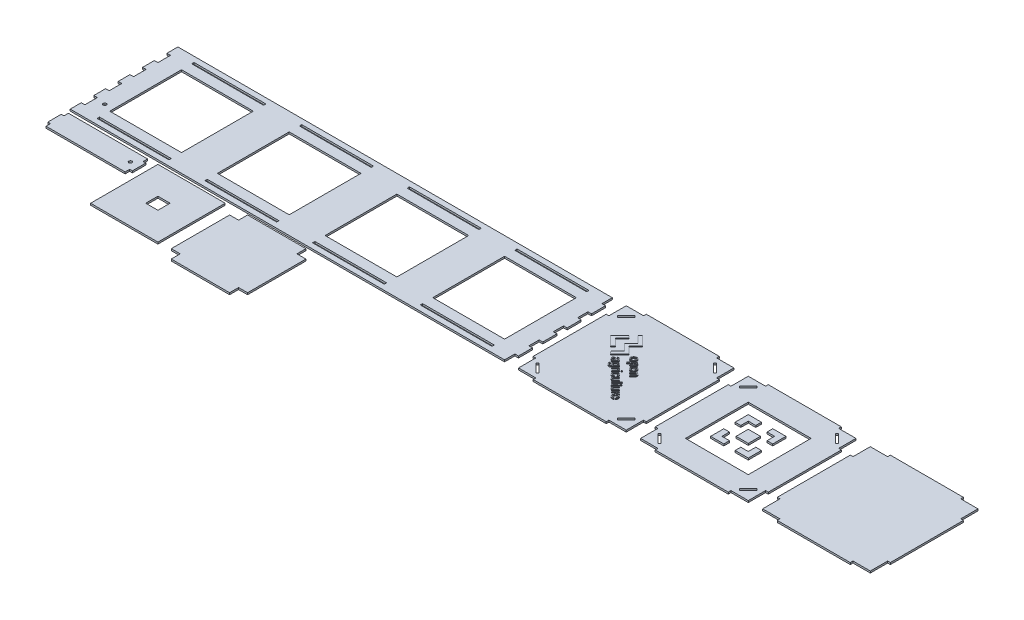
SolidWorks part; units mm, degrees
ref_plane "Front" through (0, 0, 0) normal (0, 0, 1) x (1, 0, 0)
ref_plane "Top" through (0, 0, 0) normal (0, 1, 0) x (1, 0, 0)
ref_plane "Right" through (0, 0, 0) normal (1, 0, 0) x (0, 0, -1)
sketch "Sketch1" plane through (0, 0, 0) normal (0, 1, 0) x (1, 0, 0)
  line L0 (0, 0) -> (228.6, 0) construction
  line L2 (-76.2, 76.2) -> (-76.2, -76.2) construction
  line L4 (76.2, 76.2) -> (76.2, -76.2) construction
  line L5 (-76.2, 76.2) -> (76.2, -76.2) construction
  line L6 (-76.2, -76.2) -> (76.2, 76.2) construction
  line L11 (76.2, 76.2) -> (228.6, 76.2)
  line L12 (76.2, 76.2) -> (76.2, -76.2) construction
  line L13 (76.2, -76.2) -> (228.6, -76.2)
  line L14 (228.6, 76.2) -> (228.6, -76.2) construction
  line L19 (-76.2, -76.2) -> (-228.6, -76.2)
  line L20 (-76.2, -76.2) -> (-76.2, 76.2) construction
  line L21 (-76.2, 76.2) -> (-228.6, 76.2)
  line L28 (76.2, -76.2) -> (-76.2, -76.2)
  line L34 (76.2, 76.2) -> (-76.2, 76.2)
  line L35 (-228.6, 76.2) -> (-228.6, -76.2) construction
  line L43 (-228.6, 76.2) -> (-381, 76.2)
  line L44 (-381, 76.2) -> (-381, -76.2) construction
  line L45 (-381, -76.2) -> (-228.6, -76.2)
  line L46 (228.6, 76.2) -> (228.6, 61.6712)
  line L47 (228.6, 61.6712) -> (233.68, 61.6712)
  line L48 (233.68, 61.6712) -> (233.68, 41.7322)
  line L49 (233.68, 41.7322) -> (228.6, 41.7322)
  line L50 (228.6, 41.7322) -> (228.6, 27.2034)
  line L51 (228.6, 27.2034) -> (233.68, 27.2034)
  line L63 (233.68, 27.2034) -> (233.68, 7.2644)
  line L64 (233.68, 7.2644) -> (228.6, 7.2644)
  line L65 (228.6, 7.2644) -> (228.6, -7.2644)
  line L66 (228.6, -7.2644) -> (233.68, -7.2644)
  line L67 (233.68, -7.2644) -> (233.68, -27.2034)
  line L68 (233.68, -27.2034) -> (228.6, -27.2034)
  line L69 (228.6, -27.2034) -> (228.6, -41.7322)
  line L70 (228.6, -41.7322) -> (233.68, -41.7322)
  line L71 (233.68, -41.7322) -> (233.68, -61.6712)
  line L72 (233.68, -61.6712) -> (228.6, -61.6712)
  line L73 (228.6, -61.6712) -> (228.6, -76.2)
  line L74 (-381, 76.2) -> (-386.08, 76.2)
  line L76 (-386.08, 60.5917) -> (-381, 60.5917)
  line L78 (-381, 42.8117) -> (-386.08, 42.8117)
  line L80 (-386.08, 26.1239) -> (-381, 26.1239)
  line L82 (-381, 8.3439) -> (-386.08, 8.3439)
  line L84 (-386.08, -8.3439) -> (-381, -8.3439)
  line L86 (-381, -26.1239) -> (-386.08, -26.1239)
  line L88 (-386.08, -42.8117) -> (-381, -42.8117)
  line L90 (-381, -60.5917) -> (-386.08, -60.5917)
  line L92 (-386.08, -76.2) -> (-381, -76.2)
  line L93 (233.68, 17.2339) -> (-381, 17.2339) construction
  line L94 (-381, 51.7017) -> (233.68, 51.7017) construction
  line L95 (-386.08, 76.2) -> (-386.08, 60.5917)
  line L96 (-386.08, 42.8117) -> (-386.08, 26.1239)
  line L97 (-381, 60.5917) -> (-381, 42.8117)
  line L98 (-381, 26.1239) -> (-381, 8.3439)
  line L99 (-381, -8.3439) -> (-381, -26.1239)
  line L100 (-381, -42.8117) -> (-381, -60.5917)
  line L101 (-381, -51.7017) -> (233.68, -51.7017) construction
  line L102 (-381, -17.2339) -> (233.68, -17.2339) construction
  line L103 (-386.08, 8.3439) -> (-386.08, -8.3439)
  line L104 (-386.08, -26.1239) -> (-386.08, -42.8117)
  line L105 (-386.08, -60.5917) -> (-386.08, -76.2)
  point P0 (0, 0)
  point P56 (-406.2048, -26.1239)
  point P57 (-388.4215, 60.5917)
  point P58 (-409.3463, 42.8117)
  point P59 (-388.4448, 60.5917)
  dimension "D1" = 152.4
  dimension "D2" = 152.4
  dimension "D3" = 5.08
  dimension "D4" = 19.939
  dimension "D5" = 17.78
extrude "Boss-Extrude1" add sketch "Sketch1" along normal blind 2.54
sketch "Sketch4" plane through (0, 2.54, 0) normal (0, 1, 0) x (1, 0, 0)
  line L0 (-228.6, 76.2) -> (-228.6, -76.2) construction
  line L1 (-228.6, 76.2) -> (-228.6, -76.2)
  line L2 (-76.2, 76.2) -> (-76.2, -76.2) construction
  line L3 (-76.2, 76.2) -> (-76.2, -76.2)
  line L4 (76.2, 76.2) -> (76.2, -76.2) construction
  line L5 (76.2, 76.2) -> (76.2, -76.2)
sketch "Sketch5" plane through (0, 2.54, 0) normal (0, 1, 0) x (1, 0, 0)
  line L0 (-381, -8.3439) -> (-381, 8.3439) construction
  line L1 (-228.6, 0) -> (-381, 0) construction
  line L2 (-228.6, 76.2) -> (-228.6, -76.2) construction
  line L3 (-228.6, 0) -> (-76.2, 0) construction
  line L4 (-76.2, 76.2) -> (-76.2, -76.2) construction
  line L5 (-76.2, 0) -> (76.2, 0) construction
  line L6 (76.2, 76.2) -> (76.2, -76.2) construction
  line L7 (76.2, 0) -> (228.6, 0) construction
  line L8 (228.6, -7.2644) -> (228.6, 7.2644) construction
  line L9 (-304.8, 0) -> (-304.8, -76.2) construction
  line L10 (-386.08, -76.2) -> (228.6, -76.2) construction
  line L11 (-152.4, 0) -> (-152.4, -76.2) construction
  line L12 (0, 0) -> (0, -76.2) construction
  line L13 (152.4, 0) -> (152.4, -76.2) construction
  line L14 (-254, -68.58) -> (-254, -76.2) construction
  line L15 (-355.6, -65.278) -> (-254, -65.278)
  line L16 (-355.6, -65.278) -> (-355.6, -68.58)
  line L17 (-355.6, -68.58) -> (-254, -68.58)
  line L18 (-254, -65.278) -> (-254, -68.58)
  line L19 (-355.6, -65.278) -> (-254, -68.58) construction
  line L20 (-355.6, -68.58) -> (-254, -65.278) construction
  line L21 (-203.2, -65.278) -> (-101.6, -65.278)
  line L22 (-203.2, -65.278) -> (-203.2, -68.58)
  line L23 (-203.2, -68.58) -> (-101.6, -68.58)
  line L24 (-101.6, -65.278) -> (-101.6, -68.58)
  line L25 (-203.2, -65.278) -> (-101.6, -68.58) construction
  line L26 (-203.2, -68.58) -> (-101.6, -65.278) construction
  line L27 (-50.8, -68.58) -> (50.8, -68.58)
  line L28 (-50.8, -68.58) -> (-50.8, -65.278)
  line L29 (-50.8, -65.278) -> (50.8, -65.278)
  line L30 (50.8, -68.58) -> (50.8, -65.278)
  line L31 (-50.8, -68.58) -> (50.8, -65.278) construction
  line L32 (-50.8, -65.278) -> (50.8, -68.58) construction
  line L33 (101.6, -68.58) -> (203.2, -68.58)
  line L34 (101.6, -68.58) -> (101.6, -65.278)
  line L35 (101.6, -65.278) -> (203.2, -65.278)
  line L36 (203.2, -68.58) -> (203.2, -65.278)
  line L37 (101.6, -68.58) -> (203.2, -65.278) construction
  line L38 (101.6, -65.278) -> (203.2, -68.58) construction
  line L39 (101.6, 65.278) -> (203.2, 68.58) construction
  line L40 (101.6, 68.58) -> (203.2, 65.278) construction
  line L41 (-50.8, 65.278) -> (50.8, 68.58) construction
  line L42 (-50.8, 68.58) -> (50.8, 65.278) construction
  line L43 (-203.2, 68.58) -> (-101.6, 65.278) construction
  line L44 (-203.2, 65.278) -> (-101.6, 68.58) construction
  line L45 (-355.6, 68.58) -> (-254, 65.278) construction
  line L46 (-355.6, 65.278) -> (-254, 68.58) construction
  line L47 (-254, 68.58) -> (-254, 76.2) construction
  line L48 (203.2, 68.58) -> (203.2, 65.278)
  line L49 (101.6, 65.278) -> (203.2, 65.278)
  line L50 (101.6, 68.58) -> (101.6, 65.278)
  line L51 (101.6, 68.58) -> (203.2, 68.58)
  line L52 (50.8, 68.58) -> (50.8, 65.278)
  line L53 (-50.8, 65.278) -> (50.8, 65.278)
  line L54 (-50.8, 68.58) -> (-50.8, 65.278)
  line L55 (-50.8, 68.58) -> (50.8, 68.58)
  line L56 (-101.6, 65.278) -> (-101.6, 68.58)
  line L57 (-203.2, 68.58) -> (-101.6, 68.58)
  line L58 (-203.2, 65.278) -> (-203.2, 68.58)
  line L59 (-203.2, 65.278) -> (-101.6, 65.278)
  line L60 (-254, 65.278) -> (-254, 68.58)
  line L61 (-355.6, 68.58) -> (-254, 68.58)
  line L62 (-355.6, 65.278) -> (-355.6, 68.58)
  line L63 (-355.6, 65.278) -> (-254, 65.278)
  line L65 (-355.6, 50.8) -> (-254, 50.8)
  line L66 (-355.6, 50.8) -> (-355.6, -50.8)
  line L67 (-355.6, -50.8) -> (-254, -50.8)
  line L68 (-254, 50.8) -> (-254, -50.8)
  line L69 (-355.6, 50.8) -> (-254, -50.8) construction
  line L70 (-355.6, -50.8) -> (-254, 50.8) construction
  line L71 (-203.2, 50.8) -> (-101.6, 50.8)
  line L72 (-203.2, 50.8) -> (-203.2, -50.8)
  line L73 (-203.2, -50.8) -> (-101.6, -50.8)
  line L74 (-101.6, 50.8) -> (-101.6, -50.8)
  line L75 (-203.2, 50.8) -> (-101.6, -50.8) construction
  line L76 (-203.2, -50.8) -> (-101.6, 50.8) construction
  line L77 (-50.8, 50.8) -> (50.8, 50.8)
  line L78 (-50.8, 50.8) -> (-50.8, -50.8)
  line L79 (-50.8, -50.8) -> (50.8, -50.8)
  line L80 (50.8, 50.8) -> (50.8, -50.8)
  line L81 (-50.8, 50.8) -> (50.8, -50.8) construction
  line L82 (-50.8, -50.8) -> (50.8, 50.8) construction
  line L83 (101.6, 50.8) -> (203.2, 50.8)
  line L84 (101.6, 50.8) -> (101.6, -50.8)
  line L85 (101.6, -50.8) -> (203.2, -50.8)
  line L86 (203.2, 50.8) -> (203.2, -50.8)
  line L87 (101.6, 50.8) -> (203.2, -50.8) construction
  line L88 (101.6, -50.8) -> (203.2, 50.8) construction
  circle A0 centre (-367.6, -45.8) radius 2.2225
  point P27 (-304.8, -66.929)
  point P32 (-152.4, -66.929)
  point P37 (0, -66.929)
  point P42 (152.4, -66.929)
  point P66 (152.4, 66.929)
  point P67 (0, 66.929)
  point P68 (-152.4, 66.929)
  point P69 (-304.8, 66.929)
  dimension "D5" = 4.445
  dimension "D7" = 5
  dimension "D1" = 7.62
  dimension "D2" = 3.302
  dimension "D3" = 101.6
  dimension "D4" = 101.6
  dimension "D6" = 12
extrude "Cut-Extrude2" cut sketch "Sketch5" against normal through all
sketch "Sketch6" plane through (0, 0, 0) normal (0, 1, 0) x (1, 0, 0)
  line L0 (0, 0) -> (324.5769, 0) construction
  line L1 (324.5769, 0) -> (324.5769, 78.105) construction
  line L2 (248.3769, 76.2) -> (400.7769, 76.2) construction
  line L3 (248.3769, 76.2) -> (248.3769, -76.2) construction
  line L4 (248.3769, -76.2) -> (400.7769, -76.2) construction
  line L5 (400.7769, 76.2) -> (400.7769, -76.2) construction
  line L6 (248.3769, 76.2) -> (400.7769, -76.2) construction
  line L7 (248.3769, -76.2) -> (400.7769, 76.2) construction
  line L8 (324.5769, 0) -> (402.6819, 0) construction
  line L9 (324.5769, 0) -> (324.5769, -78.105) construction
  line L10 (248.3769, 51.689) -> (248.3769, 76.2)
  line L11 (272.8879, 80.01) -> (376.2659, 80.01)
  line L12 (272.8879, 80.01) -> (272.8879, 76.2)
  line L13 (272.8879, 76.2) -> (376.2659, 76.2) construction
  line L14 (376.2659, 80.01) -> (376.2659, 76.2)
  line L15 (272.8879, 80.01) -> (376.2659, 76.2) construction
  line L16 (272.8879, 76.2) -> (376.2659, 80.01) construction
  line L17 (404.5869, -51.689) -> (400.7769, -51.689)
  line L18 (404.5869, -51.689) -> (404.5869, 51.689)
  line L19 (404.5869, 51.689) -> (400.7769, 51.689)
  line L20 (400.7769, -51.689) -> (400.7769, 51.689) construction
  line L21 (404.5869, -51.689) -> (400.7769, 51.689) construction
  line L22 (404.5869, 51.689) -> (400.7769, -51.689) construction
  line L23 (272.8879, -80.01) -> (376.2659, -80.01)
  line L24 (272.8879, -80.01) -> (272.8879, -76.2)
  line L25 (272.8879, -76.2) -> (376.2659, -76.2) construction
  line L26 (376.2659, -80.01) -> (376.2659, -76.2)
  line L27 (272.8879, -80.01) -> (376.2659, -76.2) construction
  line L28 (272.8879, -76.2) -> (376.2659, -80.01) construction
  line L29 (244.5669, 51.689) -> (248.3769, 51.689)
  line L30 (244.5669, 51.689) -> (244.5669, -51.689)
  line L31 (244.5669, -51.689) -> (248.3769, -51.689)
  line L32 (248.3769, 51.689) -> (248.3769, -51.689) construction
  line L33 (244.5669, 51.689) -> (248.3769, -51.689) construction
  line L34 (244.5669, -51.689) -> (248.3769, 51.689) construction
  line L35 (248.3769, 76.2) -> (272.8879, 76.2)
  line L36 (376.2659, 76.2) -> (400.7769, 76.2)
  line L37 (400.7769, 76.2) -> (400.7769, 51.689)
  line L38 (400.7769, -51.689) -> (400.7769, -76.2)
  line L39 (400.7769, -76.2) -> (376.2659, -76.2)
  line L40 (272.8879, -76.2) -> (248.3769, -76.2)
  line L41 (248.3769, -76.2) -> (248.3769, -51.689)
  line L42 (417.2869, 51.689) -> (417.2869, -51.689)
  line L43 (417.2869, 51.689) -> (421.0969, 51.689)
  line L44 (421.0969, 51.689) -> (421.0969, 76.2)
  line L45 (421.0969, 76.2) -> (445.6079, 76.2)
  line L46 (445.6079, 80.01) -> (445.6079, 76.2)
  line L47 (445.6079, 80.01) -> (548.9859, 80.01)
  line L48 (548.9859, 80.01) -> (548.9859, 76.2)
  line L49 (548.9859, 76.2) -> (573.4969, 76.2)
  line L50 (573.4969, 76.2) -> (573.4969, 51.689)
  line L51 (577.3069, 51.689) -> (573.4969, 51.689)
  line L52 (577.3069, -51.689) -> (577.3069, 51.689)
  line L53 (577.3069, -51.689) -> (573.4969, -51.689)
  line L54 (573.4969, -51.689) -> (573.4969, -76.2)
  line L55 (573.4969, -76.2) -> (548.9859, -76.2)
  line L56 (548.9859, -80.01) -> (548.9859, -76.2)
  line L57 (445.6079, -80.01) -> (548.9859, -80.01)
  line L58 (445.6079, -80.01) -> (445.6079, -76.2)
  line L59 (445.6079, -76.2) -> (421.0969, -76.2)
  line L60 (421.0969, -76.2) -> (421.0969, -51.689)
  line L61 (417.2869, -51.689) -> (421.0969, -51.689)
  line L62 (421.0969, 76.2) -> (573.4969, -76.2) construction
  line L63 (590.0069, 51.689) -> (590.0069, -51.689)
  line L64 (590.0069, 51.689) -> (593.8169, 51.689)
  line L65 (593.8169, 51.689) -> (593.8169, 76.2)
  line L66 (593.8169, 76.2) -> (618.3279, 76.2)
  line L67 (618.3279, 80.01) -> (618.3279, 76.2)
  line L68 (618.3279, 80.01) -> (721.7059, 80.01)
  line L69 (721.7059, 80.01) -> (721.7059, 76.2)
  line L70 (721.7059, 76.2) -> (746.2169, 76.2)
  line L71 (746.2169, 76.2) -> (746.2169, 51.689)
  line L72 (750.0269, 51.689) -> (746.2169, 51.689)
  line L73 (750.0269, -51.689) -> (750.0269, 51.689)
  line L74 (750.0269, -51.689) -> (746.2169, -51.689)
  line L75 (746.2169, -51.689) -> (746.2169, -76.2)
  line L76 (746.2169, -76.2) -> (721.7059, -76.2)
  line L77 (721.7059, -80.01) -> (721.7059, -76.2)
  line L78 (618.3279, -80.01) -> (721.7059, -80.01)
  line L79 (618.3279, -80.01) -> (618.3279, -76.2)
  line L80 (618.3279, -76.2) -> (593.8169, -76.2)
  line L81 (593.8169, -76.2) -> (593.8169, -51.689)
  line L82 (590.0069, -51.689) -> (593.8169, -51.689)
  line L84 (452.8469, 44.45) -> (541.7469, 44.45)
  line L85 (452.8469, 44.45) -> (452.8469, -44.45)
  line L86 (452.8469, -44.45) -> (541.7469, -44.45)
  line L87 (541.7469, 44.45) -> (541.7469, -44.45)
  line L88 (452.8469, 44.45) -> (541.7469, -44.45) construction
  line L89 (452.8469, -44.45) -> (541.7469, 44.45) construction
  point P22 (246.4719, 0)
  point P67 (497.2969, 0)
  dimension "D1" = 152.4
  dimension "D2" = 152.4
  dimension "D3" = 3.81
  dimension "D4" = 103.378
  dimension "D5" = 324.5769
  dimension "D7" = 12.7
  dimension "D8" = 88.9
  dimension "D6" = 3
extrude "Boss-Extrude2" add sketch "Sketch6" along normal blind 2.54 separate body
sketch "Sketch7" plane through (0, 0, 0) normal (0, 1, 0) x (1, 0, 0)
  line L0 (-355.6, 65.278) -> (-355.6, -46.736) construction
  line L1 (-382.27, -82.55) -> (-270.256, -82.55)
  line L2 (-382.27, -82.55) -> (-382.27, -88.9)
  line L3 (-382.27, -114.3) -> (-270.256, -114.3)
  line L4 (-270.256, -82.55) -> (-270.256, -88.9)
  line L5 (-382.27, -82.55) -> (-270.256, -114.3) construction
  line L6 (-382.27, -114.3) -> (-270.256, -82.55) construction
  line L7 (-355.6, 50.8) -> (-355.6, -50.8) construction
  line L8 (-355.6, -46.736) -> (-355.6, -50.8) construction
  line L9 (248.3769, -51.689) -> (248.3769, -76.2) construction
  line L10 (248.3769, -76.2) -> (272.8879, -76.2) construction
  line L12 (-382.27, -88.9) -> (-386.08, -88.9)
  line L13 (256.6811, -55.3235) -> (269.2534, -67.8958) construction
  line L14 (256.6811, -55.3235) -> (254.3462, -57.6583) construction
  line L15 (254.3462, -57.6583) -> (266.9186, -70.2307) construction
  line L16 (269.2534, -67.8958) -> (266.9186, -70.2307) construction
  line L17 (256.6811, -55.3235) -> (266.9186, -70.2307) construction
  line L18 (254.3462, -57.6583) -> (269.2534, -67.8958) construction
  line L19 (-386.08, -88.9) -> (-386.08, -107.95)
  line L20 (-386.08, -107.95) -> (-382.27, -107.95)
  line L21 (248.3769, -51.689) -> (272.8879, -76.2) construction
  line L22 (261.7998, -62.7771) -> (260.6324, -63.9445) construction
  line L23 (-382.27, -107.95) -> (-382.27, -114.3)
  line L24 (-270.256, -88.9) -> (-266.446, -88.9)
  line L25 (-266.446, -88.9) -> (-266.446, -107.95)
  line L26 (-266.446, -107.95) -> (-270.256, -107.95)
  line L27 (-270.256, -107.95) -> (-270.256, -114.3)
  line L28 (-386.08, -76.2) -> (228.6, -76.2) construction
  line L29 (-386.08, -60.5917) -> (-386.08, -76.2) construction
  point P0 (-326.263, -98.425)
  point P14 (261.7998, -62.7771)
  point P31 (-259.0782, -103.78)
  dimension "D1" = 31.75
  dimension "D2" = 4.064
  dimension "D3" = 3.302
  dimension "D4" = 19.05
  dimension "D5" = 17.78
  dimension "D6" = 3.81
  dimension "D7" = 6.35
extrude "Boss-Extrude3" add sketch "Sketch7" along normal blind 2.54 separate body
sketch "Sketch8" plane through (0, 2.54, 0) normal (0, 1, 0) x (1, 0, 0)
  line L0 (254.3462, -57.6583) -> (266.9186, -70.2307) construction
  line L1 (269.2534, -67.8958) -> (266.9186, -70.2307) construction
  line L2 (256.6811, -55.3235) -> (269.2534, -67.8958) construction
  line L3 (256.6811, -55.3235) -> (254.3462, -57.6583) construction
  line L4 (254.3462, -57.6583) -> (266.9186, -70.2307)
  line L5 (269.2534, -67.8958) -> (266.9186, -70.2307)
  line L6 (256.6811, -55.3235) -> (269.2534, -67.8958)
  line L7 (256.6811, -55.3235) -> (254.3462, -57.6583)
  line L8 (248.3769, 76.2) -> (400.7769, -76.2) construction
  line L9 (269.2534, 67.8958) -> (256.6811, 55.3235)
  line L10 (269.2534, 67.8958) -> (266.9186, 70.2307)
  line L11 (266.9186, 70.2307) -> (254.3462, 57.6583)
  line L12 (256.6811, 55.3235) -> (254.3462, 57.6583)
  line L13 (392.4727, 55.3235) -> (379.9003, 67.8958)
  line L14 (392.4727, 55.3235) -> (394.8076, 57.6583)
  line L15 (394.8076, 57.6583) -> (382.2352, 70.2307)
  line L16 (379.9003, 67.8958) -> (382.2352, 70.2307)
  line L17 (379.9003, -67.8958) -> (392.4727, -55.3235)
  line L18 (379.9003, -67.8958) -> (382.2352, -70.2307)
  line L19 (382.2352, -70.2307) -> (394.8076, -57.6583)
  line L20 (392.4727, -55.3235) -> (394.8076, -57.6583)
  line L21 (421.0969, -51.689) -> (445.6079, -76.2) construction
  line L22 (427.0662, -57.6583) -> (429.4011, -55.3235)
  line L23 (429.4011, -55.3235) -> (441.9734, -67.8958)
  line L24 (441.9734, -67.8958) -> (439.6386, -70.2307)
  line L25 (433.3524, -63.9445) -> (435.6873, -61.6096) construction
  line L26 (427.0662, -57.6583) -> (439.6386, -70.2307)
  line L27 (421.0969, 76.2) -> (573.4969, -76.2) construction
  line L28 (429.4011, 55.3235) -> (427.0662, 57.6583)
  line L29 (439.6386, 70.2307) -> (427.0662, 57.6583)
  line L30 (439.6386, 70.2307) -> (441.9734, 67.8958)
  line L31 (441.9734, 67.8958) -> (429.4011, 55.3235)
  line L32 (552.6203, 67.8958) -> (554.9552, 70.2307)
  line L33 (567.5276, 57.6583) -> (554.9552, 70.2307)
  line L34 (567.5276, 57.6583) -> (565.1927, 55.3235)
  line L35 (565.1927, 55.3235) -> (552.6203, 67.8958)
  line L36 (565.1927, -55.3235) -> (567.5276, -57.6583)
  line L37 (554.9552, -70.2307) -> (567.5276, -57.6583)
  line L38 (554.9552, -70.2307) -> (552.6203, -67.8958)
  line L39 (552.6203, -67.8958) -> (565.1927, -55.3235)
  circle A0 centre (324.5769, 0) radius 20.7898 construction
  circle A1 centre (324.5769, 0) radius 20.7898 construction
  circle A2 centre (324.5769, 0) radius 20.7898 construction
  circle A3 centre (324.5769, 0) radius 20.7898 construction
  circle A4 centre (497.2969, 0) radius 62.8618 construction
  point P28 (324.5769, 0)
  point P43 (533.3272, -100.1408)
  point P44 (0, 0)
  point P58 (497.2969, 0)
  dimension "D1" = 4
  dimension "D2" = 4
extrude "Cut-Extrude3" cut sketch "Sketch8" against normal through all
sketch "Sketch9" plane through (0, 0, 0) normal (0, 1, 0) x (1, 0, 0)
  line L1 (-256.2997, -81.8969) -> (-161.0497, -81.8969)
  line L2 (-256.2997, -81.8969) -> (-256.2997, -177.1469)
  line L3 (-256.2997, -177.1469) -> (-161.0497, -177.1469)
  line L4 (-161.0497, -81.8969) -> (-161.0497, -177.1469)
  line L5 (-256.2997, -81.8969) -> (-161.0497, -177.1469) construction
  line L6 (-256.2997, -177.1469) -> (-161.0497, -81.8969) construction
  line L7 (-217.3107, -120.8859) -> (-200.0387, -120.8859)
  line L8 (-217.3107, -120.8859) -> (-217.3107, -138.1579)
  line L9 (-217.3107, -138.1579) -> (-200.0387, -138.1579)
  line L10 (-200.0387, -120.8859) -> (-200.0387, -138.1579)
  line L11 (-217.3107, -120.8859) -> (-200.0387, -138.1579) construction
  line L12 (-217.3107, -138.1579) -> (-200.0387, -120.8859) construction
  point P0 (-208.6747, -129.5219)
  point P5 (-208.6747, -129.5219)
  point P10 (-161.3396, -179.296)
  point P11 (-42.2319, -133.7997)
  point P12 (-208.6747, -129.5219)
  dimension "D1" = 95.25
  dimension "D2" = 95.25
  dimension "D3" = 17.272
  dimension "D4" = 17.272
extrude "Boss-Extrude4" add sketch "Sketch9" along normal blind 2.54 separate body
sketch "Sketch10" plane through (0, 2.54, 0) normal (0, 1, 0) x (1, 0, 0)
  line L0 (-254, 50.8) -> (-355.6, 50.8) construction
  line L1 (-101.6, 50.8) -> (-203.2, 50.8) construction
  line L2 (50.8, 50.8) -> (-50.8, 50.8) construction
  line L3 (203.2, 50.8) -> (101.6, 50.8) construction
  line L4 (-294.64, 50.8) -> (-314.96, 50.8)
  line L5 (-142.24, 50.8) -> (-162.56, 50.8)
  line L6 (10.16, 50.8) -> (-10.16, 50.8)
  line L7 (162.56, 50.8) -> (142.24, 50.8)
  line L8 (-355.6, -46.99) -> (-254, -46.99)
  line L9 (-304.8, -46.99) -> (-304.8, -50.8) construction
  line L14 (-355.6, 50.8) -> (-355.6, -50.8) construction
  line L15 (-254, -50.8) -> (-254, 50.8) construction
  line L16 (-355.6, -50.8) -> (-254, -50.8) construction
  line L17 (-203.2, -46.99) -> (-101.6, -46.99)
  line L18 (-203.2, 50.8) -> (-203.2, -50.8) construction
  line L19 (-101.6, -50.8) -> (-101.6, 50.8) construction
  line L20 (-50.8, -46.99) -> (50.8, -46.99)
  line L21 (-50.8, 50.8) -> (-50.8, -50.8) construction
  line L22 (50.8, -50.8) -> (50.8, 50.8) construction
  line L23 (101.6, -46.99) -> (203.2, -46.99)
  line L24 (101.6, 50.8) -> (101.6, -50.8) construction
  line L25 (203.2, -50.8) -> (203.2, 50.8) construction
  line L26 (-266.446, -88.9) -> (-270.256, -88.9) construction
  arc A0 (-314.96, 50.8) -> (-294.64, 50.8) centre (-304.8, 50.8) ccw
  arc A1 (-162.56, 50.8) -> (-142.24, 50.8) centre (-152.4, 50.8) ccw
  arc A2 (-10.16, 50.8) -> (10.16, 50.8) centre (0, 50.8) ccw
  arc A3 (142.24, 50.8) -> (162.56, 50.8) centre (152.4, 50.8) ccw
  dimension "D1" = 20.32
sketch "Sketch11" plane through (0, 0, 0) normal (0, 1, 0) x (1, 0, 0)
  line L0 (-203.2, -50.8) -> (-203.2, -65.278) construction
  line L5 (-130.8134, -93.2066) -> (-48.2634, -93.2066) construction
  line L6 (-130.8134, -93.2066) -> (-130.8134, -175.7566) construction
  line L7 (-130.8134, -175.7566) -> (-48.2634, -175.7566) construction
  line L8 (-48.2634, -93.2066) -> (-48.2634, -175.7566) construction
  line L9 (-130.8134, -93.2066) -> (-48.2634, -175.7566) construction
  line L10 (-130.8134, -175.7566) -> (-48.2634, -93.2066) construction
  line L11 (-130.8134, -93.2066) -> (-143.5134, -93.2066)
  line L12 (-143.5134, -93.2066) -> (-143.5134, -175.7566)
  line L13 (-143.5134, -175.7566) -> (-130.8134, -175.7566)
  line L14 (-130.8134, -93.2066) -> (-130.8134, -80.5066)
  line L15 (-130.8134, -80.5066) -> (-48.2634, -80.5066)
  line L16 (-48.2634, -80.5066) -> (-48.2634, -93.2066)
  line L17 (-48.2634, -93.2066) -> (-35.5634, -93.2066)
  line L18 (-35.5634, -93.2066) -> (-35.5634, -175.7566)
  line L19 (-35.5634, -175.7566) -> (-48.2634, -175.7566)
  line L20 (-48.2634, -175.7566) -> (-48.2634, -188.4566)
  line L21 (-48.2634, -188.4566) -> (-130.8134, -188.4566)
  line L22 (-130.8134, -188.4566) -> (-130.8134, -175.7566)
  point P0 (-89.5384, -134.4816)
  point P17 (-35.5634, -175.7566)
  dimension "D1" = 82.55
  dimension "D2" = 82.55
  dimension "D3" = 12.7
extrude "Boss-Extrude5" add sketch "Sketch11" along normal blind 2.54 separate body
sketch "Sketch12" plane through (0, 2.54, 0) normal (0, 1, 0) x (1, 0, 0)
  line L0 (-130.8134, -93.2066) -> (-48.2634, -93.2066)
  line L1 (-48.2634, -93.2066) -> (-48.2634, -175.7566)
  line L2 (-48.2634, -175.7566) -> (-130.8134, -175.7566)
  line L3 (-130.8134, -93.2066) -> (-130.8134, -175.7566)
sketch "Sketch13" plane through (0, 0, 0) normal (0, 1, 0) x (1, 0, 0)
  line L19 (297.6119, 50.056) -> (310.5061, 37.1618)
  line L20 (310.5061, 37.1618) -> (300.9269, 27.5825)
  line L21 (300.9269, 27.5825) -> (310.4833, 18.0261)
  line L22 (310.4833, 18.0261) -> (297.4375, 4.9804)
  line L23 (297.4375, 4.9804) -> (294.4218, 8.4118)
  line L24 (294.4218, 8.4118) -> (303.9904, 17.9804)
  line L25 (303.9904, 17.9804) -> (294.4569, 27.5139)
  line L26 (294.4569, 27.5139) -> (304.0819, 37.1389)
  line L27 (304.0819, 37.1389) -> (294.3883, 46.8325)
  line L28 (294.3883, 46.8325) -> (297.6119, 50.056)
  line L29 (288.0326, 40.4768) -> (291.279, 37.2303)
  line L30 (291.279, 37.2303) -> (281.6084, 27.5597)
  line L31 (281.6084, 27.5597) -> (291.2562, 17.9118)
  line L32 (291.2562, 17.9118) -> (288.0098, 14.6654)
  line L33 (288.0098, 14.6654) -> (275.1155, 27.5597)
  line L34 (275.1155, 27.5597) -> (288.0326, 40.4768)
  line L35 (272.8879, -80.01) -> (376.2659, -80.01) construction
  line L36 (298.4855, 4.9804) -> (352.3895, -48.9236) construction
  line L37 (314.1861, 15.271) -> (389.6648, -60.2077) construction
  line L38 (262.9673, 61.6096) -> (386.1865, -61.6096) construction
  line L39 (256.6811, 55.3235) -> (269.2534, 67.8958) construction
  line L40 (392.4727, -55.3235) -> (379.9003, -67.8958) construction
  text T3 "open" font "Arial" height in points 44
  text T4 " agriculture" font "Arial" height in points 44
  dimension "D2" = 31.75
  dimension "D3" = 45
sketch "Sketch14" plane through (0, 2.54, 0) normal (0, 1, 0) x (1, 0, 0)
  line L0 (-266.446, -98.425) -> (-278.6685, -98.425) construction
  line L1 (-266.446, -107.95) -> (-266.446, -88.9) construction
  circle A0 centre (-278.6685, -98.425) radius 2.2225
  circle A1 centre (-367.6, -45.8) radius 2.2225 construction
  dimension "D1" = 10
extrude "Cut-Extrude4" cut sketch "Sketch14" against normal through all
sketch "Sketch15" plane through (0, 2.54, 0) normal (0, 1, 0) x (1, 0, 0)
  line L0 (452.8469, 44.45) -> (541.7469, -44.45) construction
  line L1 (-200.0387, -138.1579) -> (-200.0387, -120.8859) construction
  line L2 (488.6609, 8.636) -> (505.9329, 8.636)
  line L3 (488.6609, 8.636) -> (488.6609, -8.636)
  line L4 (488.6609, -8.636) -> (505.9329, -8.636)
  line L5 (505.9329, 8.636) -> (505.9329, -8.636)
  line L6 (488.6609, 8.636) -> (505.9329, -8.636) construction
  line L7 (488.6609, -8.636) -> (505.9329, 8.636) construction
  line L8 (541.7469, 44.45) -> (452.8469, -44.45) construction
  line L9 (497.2969, 18.636) -> (497.2969, 26.636) construction
  line L10 (470.6609, 26.636) -> (523.9329, 26.636) construction
  line L11 (470.6609, 26.636) -> (470.6609, -26.636) construction
  line L12 (470.6609, -26.636) -> (489.2969, -26.636) construction
  line L13 (523.9329, 26.636) -> (523.9329, -26.636) construction
  line L14 (470.6609, 26.636) -> (523.9329, -26.636) construction
  line L15 (470.6609, -26.636) -> (523.9329, 26.636) construction
  line L16 (515.9329, -18.636) -> (505.2969, -18.636) construction
  line L17 (515.9329, -18.636) -> (515.9329, 18.636) construction
  line L18 (515.9329, 18.636) -> (478.6609, 18.636) construction
  line L19 (478.6609, -18.636) -> (478.6609, 18.636) construction
  line L20 (515.9329, -18.636) -> (478.6609, 18.636) construction
  line L21 (515.9329, 18.636) -> (478.6609, -18.636) construction
  line L22 (470.6609, 0) -> (478.6609, 0) construction
  line L23 (497.2969, -18.636) -> (497.2969, -26.636) construction
  line L24 (515.9329, 0) -> (523.9329, 0) construction
  line L25 (470.6609, -8) -> (478.6609, -8)
  line L26 (470.6609, 8) -> (478.6609, 8)
  line L27 (505.2969, 18.636) -> (505.2969, 26.636)
  line L28 (515.9329, -8) -> (523.9329, -8)
  line L29 (489.2969, 18.636) -> (489.2969, 26.636)
  line L30 (515.9329, 8) -> (523.9329, 8)
  line L31 (515.9329, 8) -> (523.9329, 8) construction
  line L32 (489.2969, -18.636) -> (489.2969, -26.636)
  line L33 (505.2969, -18.636) -> (505.2969, -26.636)
  line L34 (489.2969, 26.636) -> (470.6609, 26.636)
  line L35 (470.6609, 26.636) -> (470.6609, 8)
  line L36 (478.6609, 8) -> (478.6609, 18.636)
  line L37 (478.6609, 18.636) -> (489.2969, 18.636)
  line L38 (505.2969, 26.636) -> (523.9329, 26.636)
  line L39 (523.9329, 26.636) -> (523.9329, 8)
  line L40 (515.9329, 8) -> (515.9329, 18.636)
  line L41 (515.9329, 18.636) -> (505.2969, 18.636)
  line L42 (515.9329, 0) -> (523.9329, 0) construction
  line L43 (515.9329, -8) -> (515.9329, -18.636)
  line L44 (523.9329, -8) -> (523.9329, -26.636)
  line L45 (523.9329, -26.636) -> (505.2969, -26.636)
  line L46 (478.6609, -8) -> (478.6609, -18.636)
  line L47 (478.6609, -18.636) -> (489.2969, -18.636)
  line L48 (505.2969, -26.636) -> (523.9329, -26.636) construction
  line L49 (489.2969, -18.636) -> (478.6609, -18.636) construction
  line L50 (489.2969, -26.636) -> (470.6609, -26.636)
  line L51 (470.6609, -26.636) -> (470.6609, -8)
  line L52 (505.2969, -18.636) -> (515.9329, -18.636)
  line L53 (497.2969, -26.636) -> (505.2969, -26.636) construction
  line L54 (489.2969, -26.636) -> (497.2969, -26.636) construction
  point P4 (497.2969, 0)
  point P14 (497.2969, 0)
  point P20 (497.2969, 0)
  point P45 (0, 0)
  point P52 (506.8219, -27.686)
  point P55 (506.8219, -27.686)
  point P56 (507.1959, -27.686)
  point P57 (519.9029, -9.525)
  dimension "D1" = 10
  dimension "D2" = 8
  dimension "D4" = 8
  dimension "D7" = 8
  dimension "D5" = 8
  dimension "D6" = 8
extrude "Boss-Extrude6" add sketch "Sketch15" along normal blind 2.54 separate body
extrude "Boss-Extrude7" add sketch "Sketch13" along normal blind 3.81 separate body
